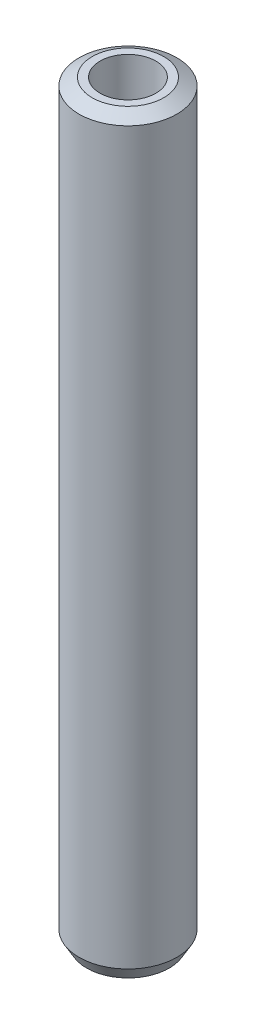
SolidWorks part; units mm, degrees
ref_plane "Front Plane" through (0, 0, 0) normal (0, 0, 1) x (1, 0, 0)
ref_plane "Top Plane" through (0, 0, 0) normal (0, 1, 0) x (1, 0, 0)
ref_plane "Right Plane" through (0, 0, 0) normal (1, 0, 0) x (0, 0, -1)
sketch "Sketch1" plane through (0, 0, 0) normal (0, 1, 0) x (1, 0, 0)
  circle A0 centre (0, 0) radius 35
  dimension "SHAFT_OD" = 70
extrude "Boss-Extrude1" add sketch "Sketch1" along normal blind 537.4257
sketch "Sketch2" plane through (0, 0, 0) normal (0, 1, 0) x (1, 0, 0)
  circle A0 centre (0, 0) radius 19.9691
  dimension "BORE_D" = 39.9382
extrude "Cut-Extrude1" cut sketch "Sketch2" along normal through all
chamfer "Chamfer1" distance 5.4425 angle 60 2 edges at (0, 537.4257, 35) (0, 0, 35) first distance on face at (0, 537.4257, 35) first distance on face at (0, 0, 19.9691)
